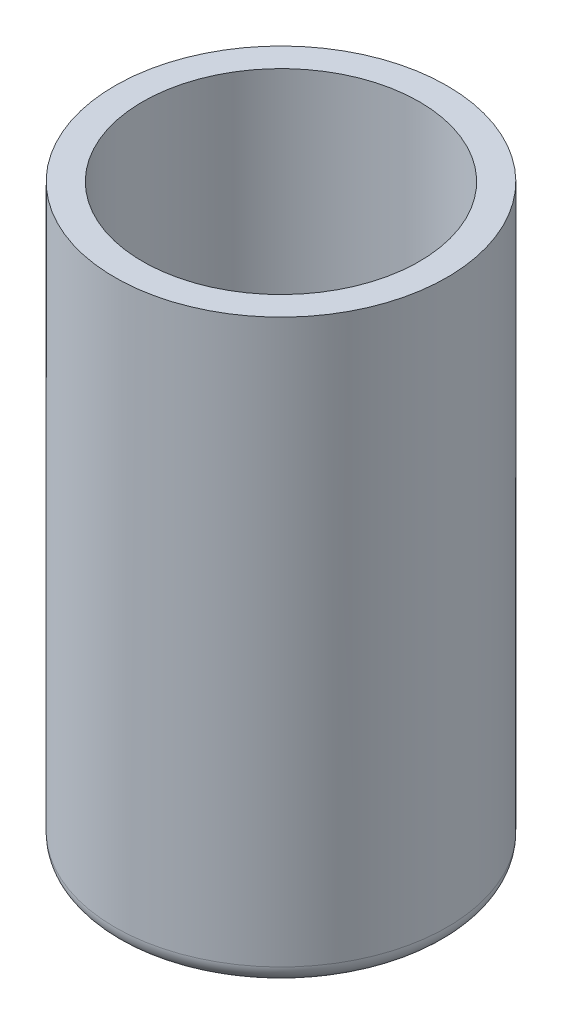
SolidWorks part; units mm, degrees
material "ПВХ Жесткий"
ref_plane "Спереди" through (0, 0, 0) normal (0, 0, 1) x (1, 0, 0)
ref_plane "Сверху" through (0, 0, 0) normal (0, 1, 0) x (1, 0, 0)
ref_plane "Справа" through (0, 0, 0) normal (1, 0, 0) x (0, 0, -1)
sketch "Эскиз1" plane through (0, 0, 0) normal (0, 0, 1) x (1, 0, 0)
  line L0 (0, 0) -> (-18, 0)
  line L1 (-18, 0) -> (-18, 63)
  line L2 (-18, 63) -> (-15, 63)
  line L3 (-15, 63) -> (-15, 3)
  line L4 (-15, 3) -> (0, 3)
  line L5 (0, 3) -> (0, 0)
  line L6 (0, 3) -> (0, 63) construction
  line L7 (-15, 63) -> (0, 63) construction
  dimension "D1" = 15
  dimension "D2" = 3
  dimension "D3" = 3
  dimension "D4" = 60
revolve "Повернуть1" add sketch "Эскиз1" angle 360 about L6
fillet "Скругление1" radius 2 1 edges at (0, 0, -18)
sketch "Эскиз2" plane through (0, 63, 0) normal (0, 1, 0) x (1, 0, 0)
  line L0 (18, 0) -> (-18, 0) construction
  circle A0 centre (0, 0) radius 18 construction
ref_plane "Симм Кювета" through (0, 0, 0) normal (0, 0, -1) x (-1, 0, 0)
